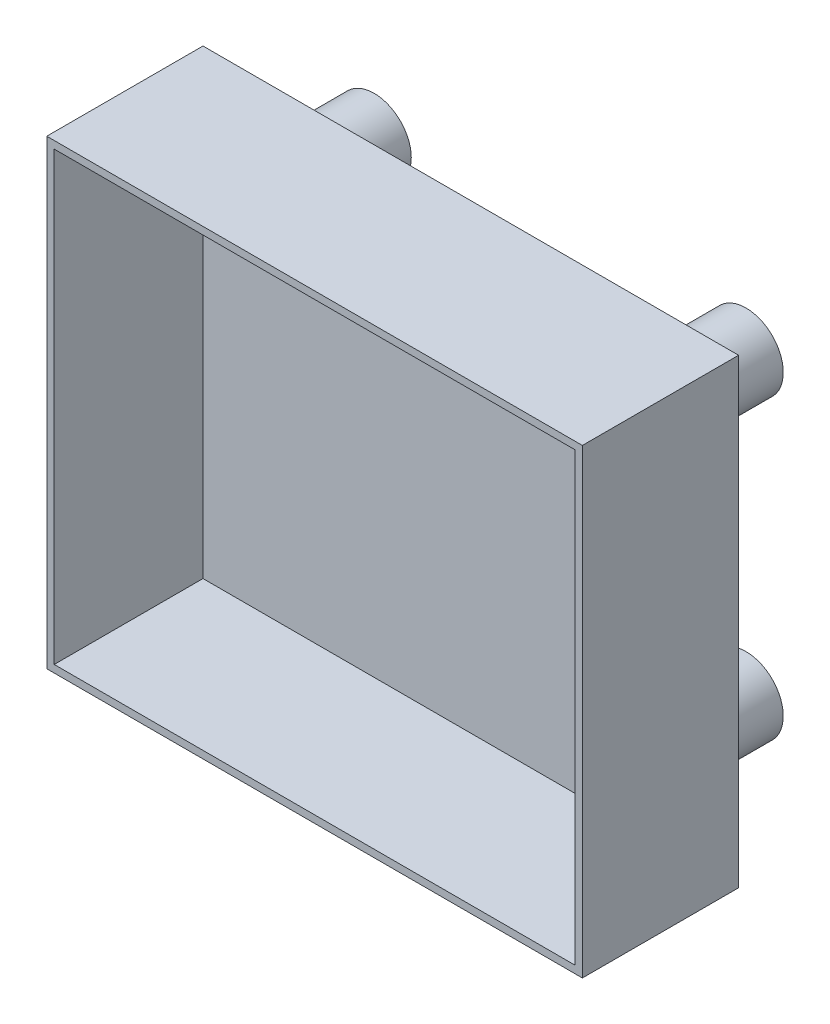
SolidWorks part; units mm, degrees
ref_plane "Front Plane" through (0, 0, 0) normal (0, 0, 1) x (1, 0, 0)
ref_plane "Top Plane" through (0, 0, 0) normal (0, 1, 0) x (1, 0, 0)
ref_plane "Right Plane" through (0, 0, 0) normal (1, 0, 0) x (0, 0, -1)
sketch "Sketch2" plane through (0, 0, 0) normal (0, 0, 1) x (1, 0, 0)
  line L1 (-88.9, -76.2) -> (88.9, -76.2)
  line L2 (-88.9, -76.2) -> (-88.9, 76.2)
  line L3 (-88.9, 76.2) -> (88.9, 76.2)
  line L4 (88.9, -76.2) -> (88.9, 76.2)
  line L5 (-88.9, -76.2) -> (88.9, 76.2) construction
  line L6 (-88.9, 76.2) -> (88.9, -76.2) construction
  point P0 (0, 0)
  dimension "D1" = 152.4
  dimension "D2" = 177.8
extrude "Boss-Extrude1" add sketch "Sketch2" along normal blind 50.8
shell "Shell2" thickness 2.54 removed face at (0, 0, 50.8) outward yes
sketch "Sketch5" plane through (0, 0, 0) normal (0, 0, 1) x (1, 0, 0)
  line L0 (91.44, 78.74) -> (-91.44, 78.74) construction
  line L2 (-91.44, -78.74) -> (91.44, -78.74) construction
  line L3 (91.44, -78.74) -> (91.44, 78.74) construction
  circle A0 centre (-63.5, -50.8) radius 12.7
  circle A1 centre (63.5, -50.8) radius 12.7
  circle A2 centre (63.5, 50.8) radius 12.7
  circle A3 centre (-63.5, 50.8) radius 12.7
  dimension "D1" = 25.4
  dimension "D2" = 25.4
  dimension "D3" = 25.4
  dimension "D4" = 25.4
  dimension "D5" = 101.6
  dimension "D6" = 101.6
  dimension "D7" = 27.94
  dimension "D8" = 27.94
  dimension "D9" = 27.94
  dimension "D10" = 27.94
  dimension "D11" = 127
  dimension "D12" = 27.94
extrude "Boss-Extrude3" add sketch "Sketch5" against normal blind 33.02
